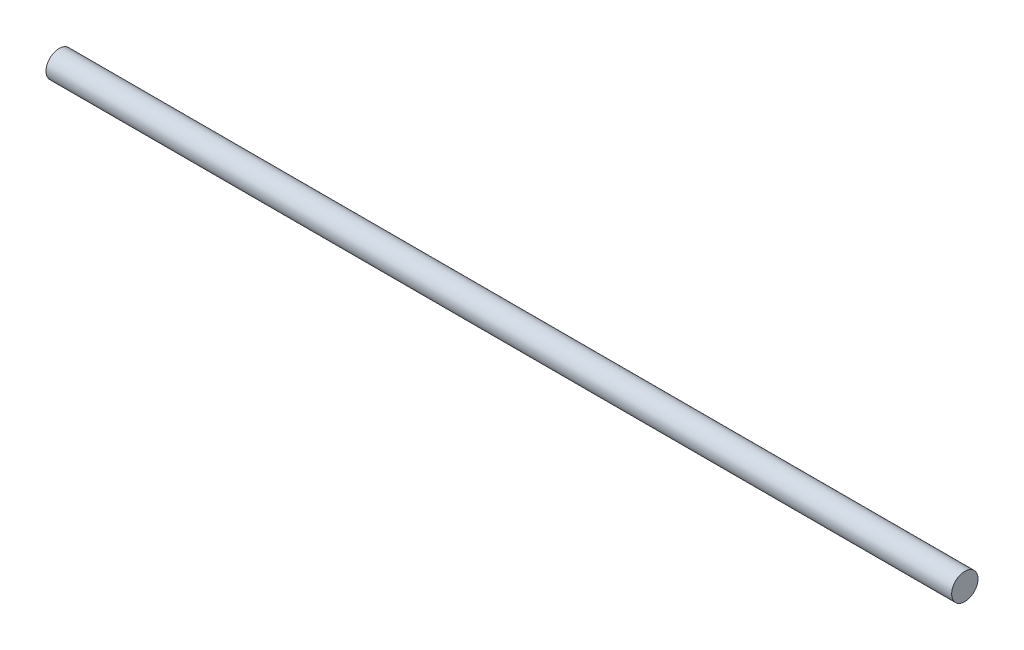
SolidWorks part; units mm, degrees
ref_plane "Top" through (0, 0, 0) normal (0, 0, 1) x (1, 0, 0)
ref_plane "Front" through (0, 0, 0) normal (0, 1, 0) x (1, 0, 0)
ref_plane "Right" through (0, 0, 0) normal (1, 0, 0) x (0, 0, -1)
sketch "Section Sketch" plane through (0, 0, 0) normal (1, 0, 0) x (0, 0, -1)
  circle A0 centre (0, 0) radius 4
  dimension "Diameter" = 8
extrude "Extrude Length" add sketch "Section Sketch" along normal blind 275
